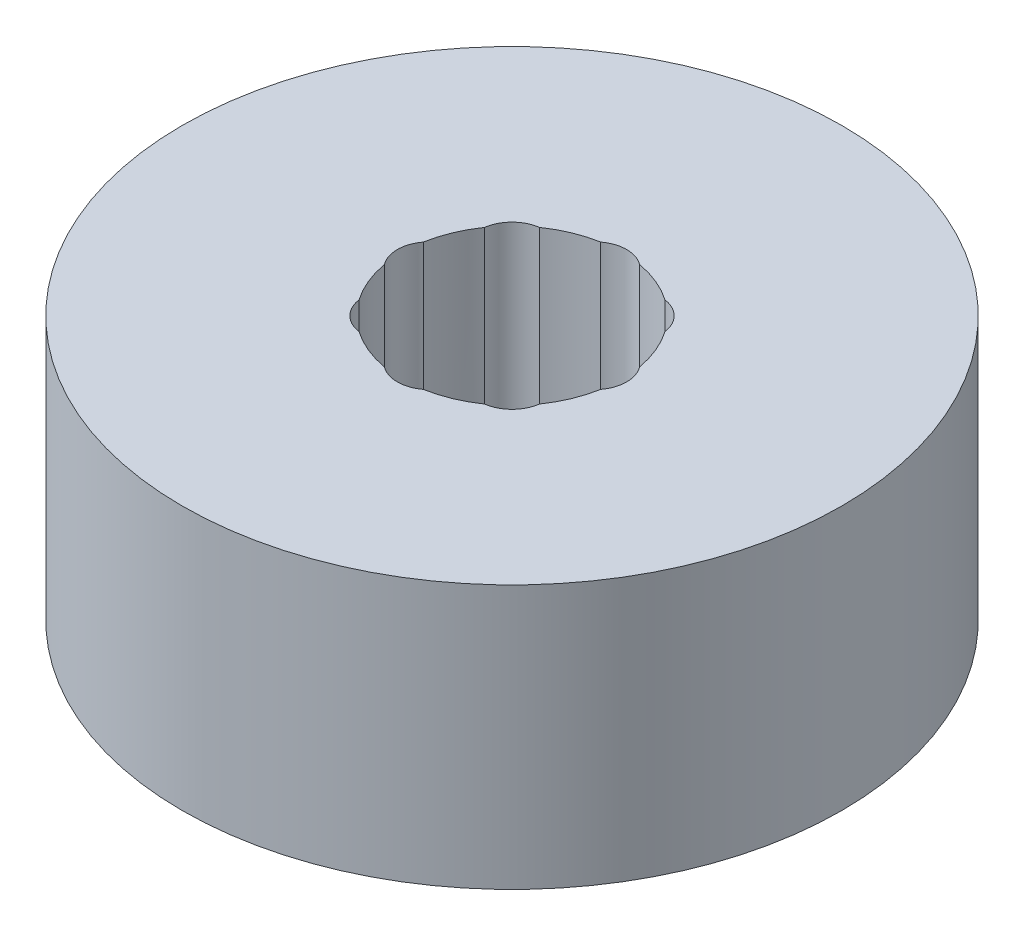
SolidWorks part; units mm, degrees
ref_plane "Front Plane" through (0, 0, 0) normal (0, 0, 1) x (1, 0, 0)
ref_plane "Top Plane" through (0, 0, 0) normal (0, 1, 0) x (1, 0, 0)
ref_plane "Right Plane" through (0, 0, 0) normal (1, 0, 0) x (0, 0, -1)
sketch "Sketch1" plane through (0, 0, 0) normal (0, 1, 0) x (1, 0, 0)
  circle A0 centre (0, 0) radius 22.5
  dimension "FLANGE_OD" = 45
extrude "Boss-Extrude1" add sketch "Sketch1" along normal blind 18
sketch "Sketch2" plane through (0, 0, 0) normal (0, 1, 0) x (1, 0, 0)
  circle A0 centre (0, 0) radius 7.5
  dimension "BORE_D" = 15
extrude "Cut-Extrude1" cut sketch "Sketch2" along normal through all
sketch "Sketch3" plane through (0, 18, 0) normal (0, 1, 0) x (1, 0, 0)
  circle A0 centre (0, 0) radius 5.6199 construction
  circle A1 centre (-5.6199, 0) radius 2.2064
  dimension "BOLT_D" = 4.4127
  dimension "BOLT_PCD" = 11.2399
extrude "Cut-Extrude2" cut sketch "Sketch3" against normal blind 13.9922
pattern_circular "CirPattern1" count 8 over 360 about axis through (0, 0, 0) along (0, 1, 0) of "Cut-Extrude2"
